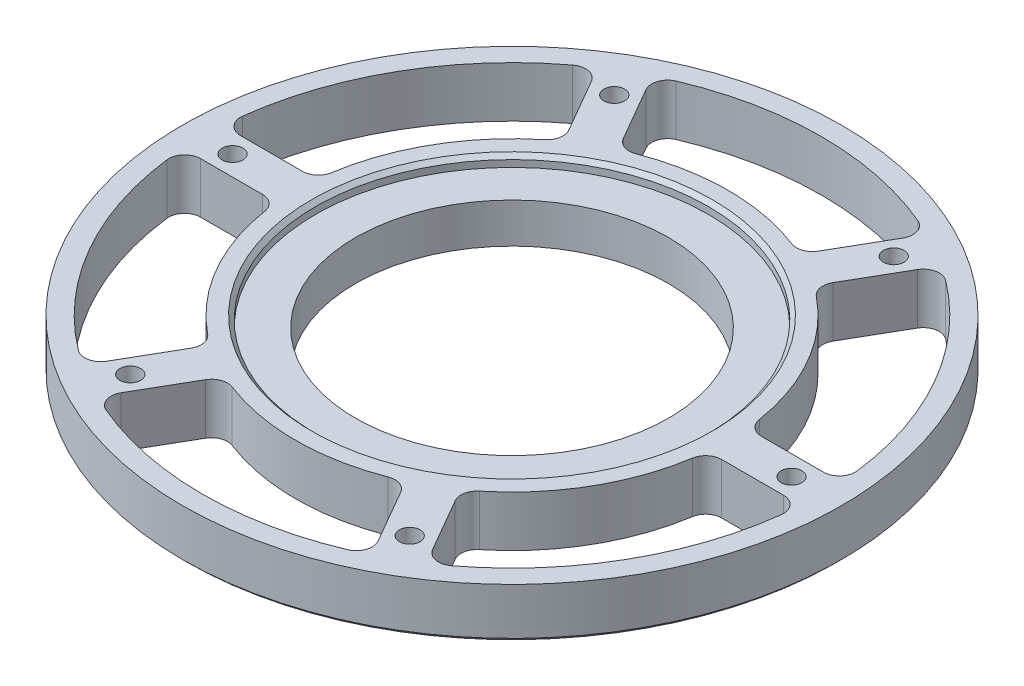
SolidWorks part; units mm, degrees
material "6061-T6 (SS)"
ref_plane "Front Plane" through (0, 0, 0) normal (0, 0, 1) x (1, 0, 0)
ref_plane "Top Plane" through (0, 0, 0) normal (0, 1, 0) x (1, 0, 0)
ref_plane "Right Plane" through (0, 0, 0) normal (1, 0, 0) x (0, 0, -1)
sketch "Sketch2" plane through (0, 0, 0) normal (1, 0, 0) x (0, 0, -1)
  line L0 (-39.2125, 0) -> (-82.55, 0)
  line L1 (-82.55, 0) -> (-82.55, 12.7)
  line L2 (-82.55, 12.7) -> (-49.2125, 12.7)
  line L3 (-49.2125, 12.7) -> (-49.2125, 10)
  line L4 (-49.2125, 10) -> (-39.2125, 10)
  line L5 (-39.2125, 10) -> (-39.2125, 0)
  dimension "D1" = 82.55
  dimension "D2" = 12.7
  dimension "D4" = 49.2125
  dimension "D5" = 10
  dimension "D3" = 10
ref_axis "Axis1" through (0, -0.9525, 0) along (0, 1, 0)
revolve "Revolve1" add sketch "Sketch2" angle 360 about axis through (0, -0.9525, 0) along (0, 1, 0)
hole_wizard "#6 (0.204) Diameter Hole1" positions "Sketch6" profile "Sketch7" hole size "#6" standard "ANSI Inch" end condition through all
sketch "Sketch6" plane through (0, 12.7, 0) normal (0, 1, 0) x (1, 0, 0)
  line L0 (0, 0) -> (-69.8201, 120.932) construction
  line L2 (0, 0) -> (0, 109.0908) construction
  point P0 (-35, 60.6218)
  dimension "D1" = 30
  dimension "D2" = 70
sketch "Sketch7" plane through (-35, 12.7, -60.6218) normal (1, 0, 0) x (0, 0, 1)
  line L0 (0, 0) -> (0, 12.7)
  line L1 (0, 12.7) -> (2.5908, 12.7)
  line L2 (2.5908, 12.7) -> (2.5908, 0)
  line L5 (2.5908, 0) -> (0, 0)
  line L11 (0, -6.35) -> (0, 107.95) construction
  dimension "Thru Hole Dia." = 5.1816
  dimension "Thru Hole Depth" = 12.7
pattern_circular "CirPattern3" count 6 over 360 about axis through (0, -0.9525, 0) along (0, 1, 0) of "#6 (0.204) Diameter Hole1"
sketch "Sketch8" plane through (0, 12.7, 0) normal (0, 1, 0) x (1, 0, 0)
  line L0 (-34.3642, 69.5205) -> (-22.6606, 49.2493)
  line L1 (34.3642, 69.5205) -> (22.6606, 49.2493)
  line L2 (0, 0) -> (-35, 60.6218) construction
  line L4 (0, 0) -> (0, 93.9995) construction
  arc A0 (-22.6606, 49.2493) -> (22.6606, 49.2493) centre (0, 0) cw
  arc A1 (-34.3642, 69.5205) -> (34.3642, 69.5205) centre (0, 0) cw
  circle A2 centre (0, 0) radius 49.2125 construction
  circle A3 centre (0, 0) radius 82.55 construction
  dimension "D1" = 5
  dimension "D2" = 5
  dimension "D3" = 5
extrude "Cut-Extrude1" cut sketch "Sketch8" against normal through all
fillet "Fillet1" radius 4 4 edges at (34.3642, 6.35, -69.5205) (22.6606, 6.35, -49.2493) (-34.3642, 6.35, -69.5205) (-22.6606, 6.35, -49.2493)
pattern_circular "CirPattern4" count 6 over 360 about axis through (0, -0.9525, 0) along (0, 1, 0) of "Cut-Extrude1", "Fillet1"
chamfer "Chamfer1" distance 1 angle 45 1 edges at (0, 12.7, -49.2125)
chamfer "Chamfer2" distance 1 angle 45 1 edges at (0, 0, -82.55)
equation "\"TubeDiameter\" = 6.500in"
equation "\"D1@Sketch2\"=\"TubeDiameter\"/2"
